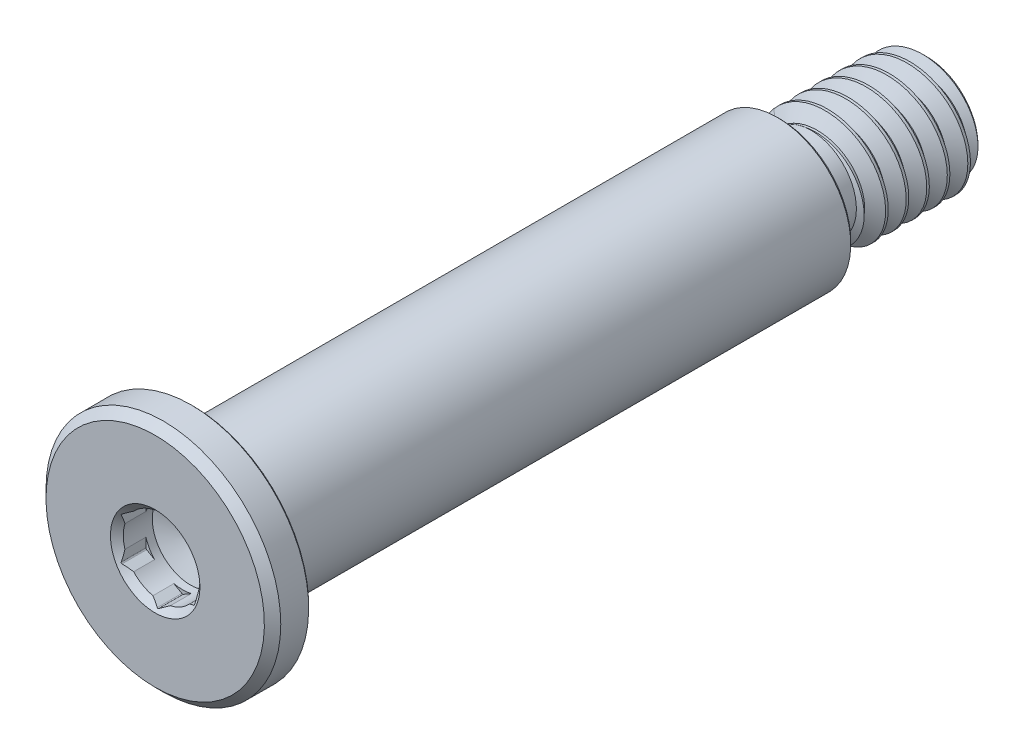
SolidWorks part; units mm, degrees
ref_plane "Front Plane" through (0, 0, 0) normal (0, 0, 1) x (1, 0, 0)
ref_plane "Top Plane" through (0, 0, 0) normal (0, 1, 0) x (1, 0, 0)
ref_plane "Right Plane" through (0, 0, 0) normal (1, 0, 0) x (0, 0, -1)
sketch "Sketch1" plane through (0, 0, 0) normal (1, 0, 0) x (0, 0, -1)
  line L0 (25, 0) -> (0, 0) construction
  line L1 (0, 0) -> (-1.3, 0) construction
  line L2 (-1.3, 4) -> (-1.3, -4) construction
  line L3 (0, 4) -> (0, -4) construction
  line L4 (20, 2) -> (25, 2) construction
  line L5 (24.9562, 2.0758) -> (25.6562, 2.0758) construction
  line L6 (25.6562, 2.0758) -> (25.3062, 1.4696) construction
  line L7 (25.3062, 1.4696) -> (24.9562, 2.0758) construction
  line L8 (25, 2) -> (25.6125, 2) construction
  line L9 (25.2625, 1.5453) -> (25.35, 1.5453) construction
  line L10 (25.3062, 1.4696) -> (25.3062, 1.5453) construction
  line L11 (25.3063, 2) -> (25.3062, 2.0758) construction
  line L12 (-1.3, 1.25) -> (-0.0938, 1.25) construction
  line L13 (-0.0938, 1.25) -> (-0.0938, -1.25) construction
  line L14 (-0.0938, -1.25) -> (-1.3, -1.25) construction
  line L15 (20, 2.5) -> (20, -2.5) construction
  line L16 (-1.3, 4) -> (0, 4) construction
  line L17 (20, -2) -> (25, -2) construction
  point P12 (-0.0938, 0)
  point P27 (20, 0)
  point P36 (23.95, -2)
  dimension "Screw Size Decimal Equivalent" = 4
  dimension "Thread Length" = 5
  dimension "Shoulder Diameter" = 5
  dimension "Head Height" = 1.3
  dimension "Head Diameter" = 8
  dimension "Drive Size" = 2.5
  dimension "Thread Pitch" = 0.7
  dimension "Pitch/8" = 0.0875
  dimension "Thread Note" = 1.05
  dimension "Shoulder Length" = 20
  dimension "Approximate Drive Depth" = 1.2063
sketch "Sketch2" plane through (0, 0, 0) normal (1, 0, 0) x (0, 0, -1)
  line L0 (-1.3, 4) -> (0, 4)
  line L1 (0, 4) -> (0, 2.5)
  line L2 (0, 2.5) -> (20, 2.5)
  line L3 (20, 2.5) -> (20, 2)
  line L4 (20, 2) -> (25, 2)
  line L5 (25, 2) -> (25, 0)
  line L6 (25, 0) -> (-1.3, 0)
  line L7 (-1.3, 0) -> (-1.3, 4)
revolve "Revolve1" add sketch "Sketch2" angle 360 about L1
chamfer "Chamfer1" distance 0.2795 angle 45 1 edges at (0, 4, 1.3)
chamfer "Chamfer4" distance 0.0699 angle 45 1 edges at (0, 4, 0)
sketch "Sketch3" plane through (0, 0, 0) normal (1, 0, 0) x (0, 0, -1)
  line L0 (0, 2.5) -> (0.5311, 2.5)
  line L1 (20, 2.5) -> (0, 2.5) construction
  line L2 (0.5311, 2.5) -> (0.3756, 2.3444)
  line L3 (0, 4) -> (0, -4) construction
  line L4 (0, 2.28) -> (0.22, 2.28) construction
  arc A0 (0.3756, 2.3444) -> (0, 2.5) centre (0.22, 2.5) cw
  dimension "D2" = 0.22
  dimension "D1" = 45
revolve "Cut-Revolve1" cut sketch "Sketch3" angle 360 about L0
sketch "Sketch4" plane through (0, 0, 0) normal (1, 0, 0) x (0, 0, -1)
  line L0 (20, 2) -> (25, 2) construction
  line L1 (20, 2) -> (21.314, 2)
  line L2 (20, 2) -> (20, 1.5428)
  line L3 (20, 1.5428) -> (21.05, 1.5428)
  line L4 (21.314, 2) -> (21.05, 1.5428)
  line L5 (20, 2.5) -> (20, -2.5) construction
  line L7 (25.2625, 1.5453) -> (25.35, 1.5453) construction
  point P8 (21.0515, 1.5453)
  dimension "D1" = 1.05
  dimension "D2" = 60
  dimension "D3" = 0.0025
revolve "Cut-Revolve2" cut sketch "Sketch4" angle 360 about L0
chamfer "Chamfer2" distance 0.1 angle 45 1 edges at (0, 2.5, -20)
fillet "Fillet1" radius 0.08 1 edges at (0, 1.5428, -20)
chamfer "Chamfer3" distance 0.2625 angle 45 1 edges at (0, 2, -25)
sketch "Sketch11" plane through (0, 0, 1.3) normal (0, 0, 1) x (1, 0, 0)
  circle A0 centre (0, 0) radius 1.3062
  dimension "D1" = 2.6125
extrude "Cut-Extrude4" cut sketch "Sketch11" against normal up to vertex (1.2063 mm away) up to point (0, 1.25, 0.0938)
sketch "Sketch5" plane through (0, 0, 1.3) normal (0, 0, 1) x (1, 0, 0)
  line L1 (0, 1.4434) -> (-1.25, 0.7217)
  line L2 (-1.25, 0.7217) -> (-1.25, -0.7217)
  line L3 (-1.25, -0.7217) -> (0, -1.4434)
  line L4 (0, -1.4434) -> (1.25, -0.7217)
  line L5 (1.25, -0.7217) -> (1.25, 0.7217)
  line L6 (1.25, 0.7217) -> (0, 1.4434)
  circle A0 centre (0, 0) radius 1.25 construction
  circle A1 centre (0, 0) radius 4 construction
extrude "Cut-Extrude1" cut sketch "Sketch5" against normal blind 0.9336
sketch "Sketch6" plane through (0, 0, 1.3) normal (0, 0, 1) x (1, 0, 0)
  circle A0 centre (0, 0) radius 1.525
  dimension "D1" = 3.05
extrude "Cut-Extrude2" cut sketch "Sketch6" against normal up to vertex (1.2063 mm away) draft 45 up to point (0, 1.25, 0.0938)
sketch "Sketch9" plane through (0, 0, 0.0938) normal (0, 0, 1) x (1, 0, 0)
  circle A0 centre (0, 0) radius 1.3062
  circle A2 centre (0, 0) radius 1.3062 construction
extrude "Cut-Extrude3" cut sketch "Sketch9" against normal through all draft 70
fillet "Fillet2" radius 0.05 6 edges at (1.25, 0.7217, 0.7924) (0, 1.4434, 0.7924) (-1.25, 0.7217, 0.7924) (0, -1.4434, 0.7924) (1.25, -0.7217, 0.7924) (-1.25, -0.7217, 0.7924)
fillet "Fillet3" radius 0.3124 1 edges at (0, 2.5, -0.5311)
ref_plane "Plane1" through (0, 0, -21.05) normal (0, 0, 1) x (1, 0, 0)
split "Split1" trim tools "Plane1" bodies to split 113 resulting bodies 109 110
sketch "Sketch7" plane through (0, 0, 0) normal (1, 0, 0) x (0, 0, -1)
  line L0 (25.2625, 1.5453) -> (25.35, 1.5453)
  line L1 (25.35, 1.5453) -> (25.6344, 2.0379)
  line L2 (25.6562, 2.0758) -> (25.3062, 1.4696) construction
  line L3 (25.6344, 2.0379) -> (24.9781, 2.0379)
  line L4 (25.3062, 1.4696) -> (24.9562, 2.0758) construction
  line L5 (24.9781, 2.0379) -> (25.2625, 1.5453)
  line L6 (25.3063, 2) -> (25.3062, 2.0758) construction
  point P12 (25.3063, 2.0379)
sketch "Sketch8" plane through (0, 0, -25) normal (0, 0, -1) x (-1, 0, 0)
  circle A0 centre (0, 0) radius 2
curve "Helix/Spiral1" pitch 0.7 height 4.65 radius 2 centre (0, 0, -25) axis (0, 0, 1) start towards (0, 1, 0)
sweep "Cut-Sweep1" cut profiles "Sketch7" path "Helix/Spiral1" align with end faces yes
ref_plane "Plane2" through (0, 0, -21.0515) normal (0, 0, 1) x (1, 0, 0)
sketch "Sketch10" plane through (0, 0, -21.0515) normal (0, 0, 1) x (1, 0, 0)
  circle A0 centre (0, 0) radius 1.5453
extrude "Boss-Extrude1" add sketch "Sketch10" along normal through all draft 60
equation "\"Pitch/8@Sketch1\" = \"Thread Pitch@Sketch1\" / 8"
equation "\"Thread Note@Sketch1\"=\"Thread Pitch@Sketch1\"*1.5"
equation "\"D1@Chamfer1\"=\"Head Height@Sketch1\"*.215"
equation "\"D1@Sketch4\"=\"Thread Pitch@Sketch1\"*1.5"
equation "\"D1@Chamfer2\"=\"Shoulder Diameter@Sketch1\"*.02"
equation "\"D1@Fillet1\" = \"D1@Chamfer2\" * .8"
equation "\"D1@Chamfer3\"=\"Thread Pitch@Sketch1\" * .375"
equation "\"D1@Sketch6\"=\"Drive Size@Sketch1\" * 1.22"
equation "\"D1@Fillet2\"=\"Drive Size@Sketch1\"*.02"
equation "\"D4@Helix/Spiral1\"=\"Thread Pitch@Sketch1\""
equation "\"D3@Helix/Spiral1\"=\"Thread Length@Sketch1\" - \"Thread Pitch@Sketch1\"*.5"
equation "\"Approximate Drive Depth@Sketch1\"=\"Drive Size@Sketch1\"*.4825"
equation "\"D1@Chamfer4\"=\"D1@Chamfer1\"*.25"
equation "\"D2@Sketch3\"=\"Shoulder Diameter@Sketch1\"*.044"
equation "\"D1@Fillet3\"=\"D2@Sketch3\" * 1.42"
equation "\"D1@Sketch11\"=\"Drive Size@Sketch1\"*1.045"
equation "\"D1@Cut-Extrude1\"=\"Approximate Drive Depth@sketch1\"*.774"
